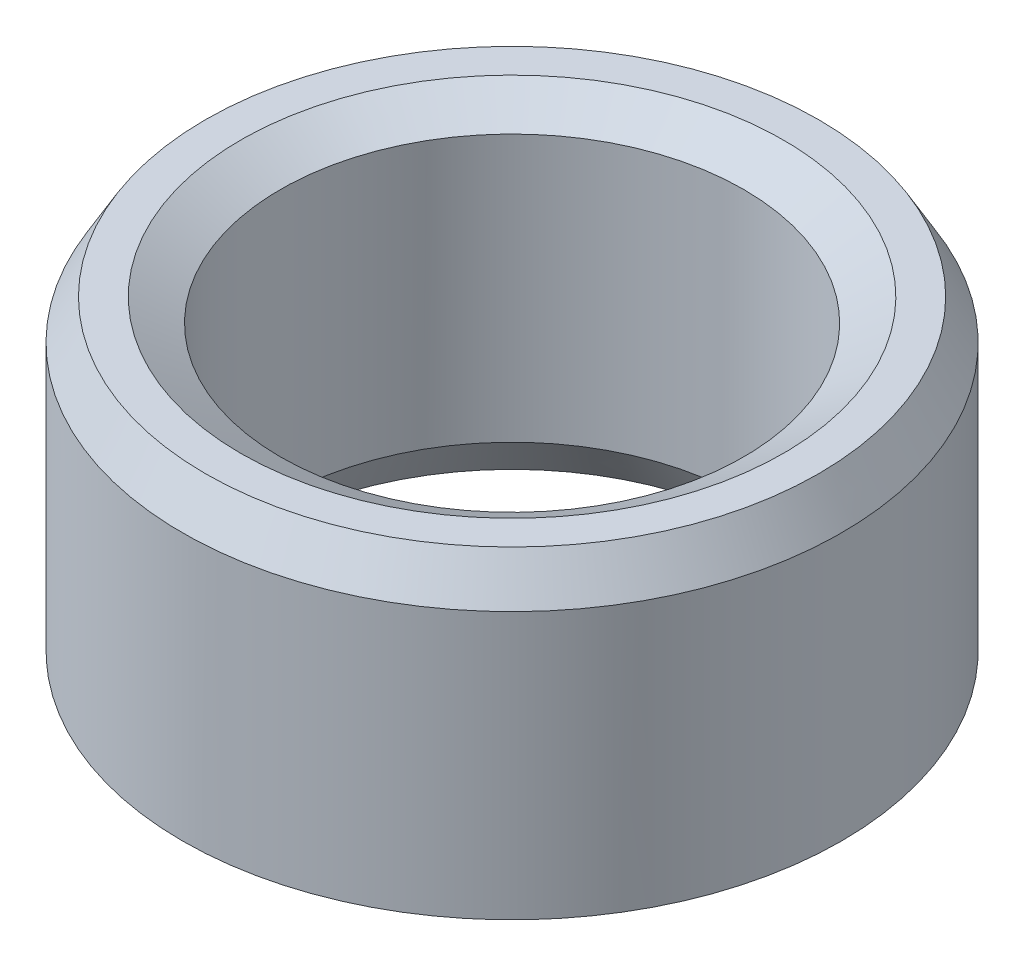
SolidWorks part; units mm, degrees
ref_plane "Front Plane" through (0, 0, 0) normal (0, 0, 1) x (1, 0, 0)
ref_plane "Top Plane" through (0, 0, 0) normal (0, 1, 0) x (1, 0, 0)
ref_plane "Right Plane" through (0, 0, 0) normal (1, 0, 0) x (0, 0, -1)
sketch "Sketch1" plane through (0, 0, 0) normal (0, 1, 0) x (1, 0, 0)
  circle A0 centre (0, 0) radius 30
  dimension "SLEEVE_OD" = 60
extrude "Boss-Extrude1" add sketch "Sketch1" along normal blind 29.9993
sketch "Sketch2" plane through (0, 0, 0) normal (0, 1, 0) x (1, 0, 0)
  circle A0 centre (0, 0) radius 21.0873
  dimension "BORE_D" = 42.1747
extrude "Cut-Extrude1" cut sketch "Sketch2" along normal through all
chamfer "Chamfer1" distance 3.6169 angle 30 4 edges at (0, 29.9993, 21.0873) (0, 0, 21.0873) (0, 0, 30) (0, 29.9993, 30) first distance on face at (0, 29.9993, 21.0873) first distance on face at (0, 0, 21.0873) first distance on face at (0, 29.9993, 30)
